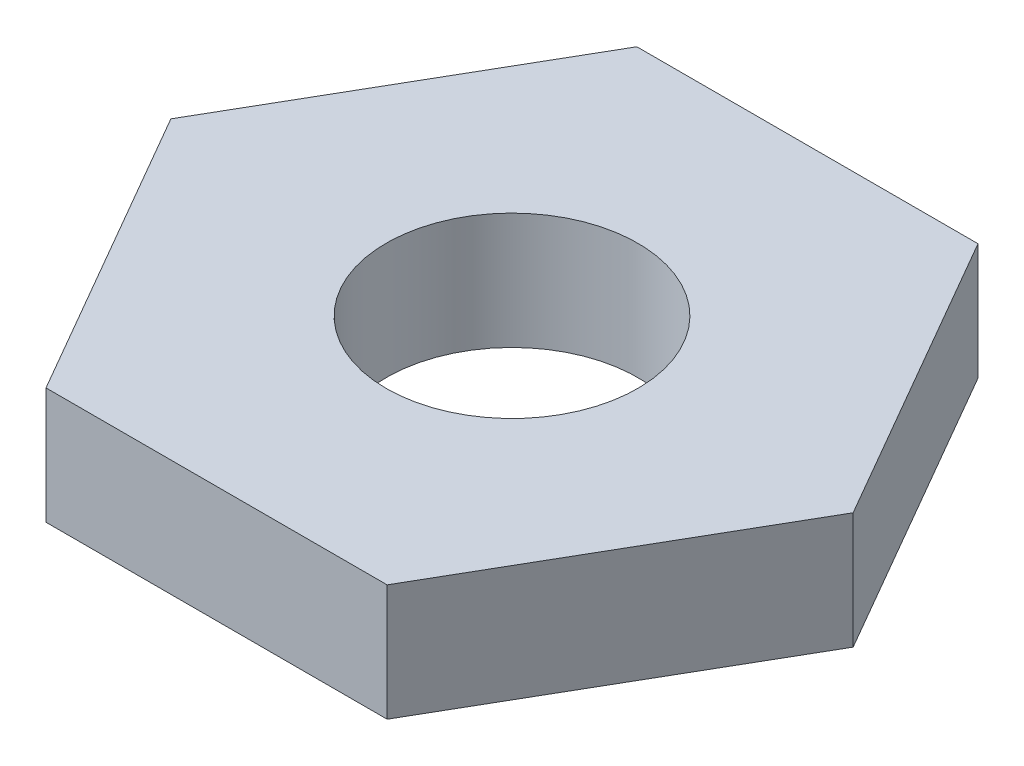
SolidWorks part; units mm, degrees
ref_plane "Front" through (0, 0, 0) normal (0, 0, 1) x (1, 0, 0)
ref_plane "Top" through (0, 0, 0) normal (0, 1, 0) x (1, 0, 0)
ref_plane "Right" through (0, 0, 0) normal (1, 0, 0) x (0, 0, -1)
sketch "Sketch1" plane through (0, 0, 0) normal (0, 1, 0) x (1, 0, 0)
  line L1 (5.4226, 0) -> (2.7113, 4.6962)
  line L2 (2.7113, 4.6962) -> (-2.7113, 4.6962)
  line L3 (-2.7113, 4.6962) -> (-5.4226, 0)
  line L4 (-5.4226, 0) -> (-2.7113, -4.6962)
  line L5 (-2.7113, -4.6962) -> (2.7113, -4.6962)
  line L6 (2.7113, -4.6962) -> (5.4226, 0)
  circle A0 centre (0, 0) radius 4.6962 construction
  circle A1 centre (0, 0) radius 2
  point P10 (0, 2)
  dimension "D1" = 4
  dimension "D2" = 2.6962
extrude "Boss-Extrude1" add sketch "Sketch1" along normal blind 1.85
